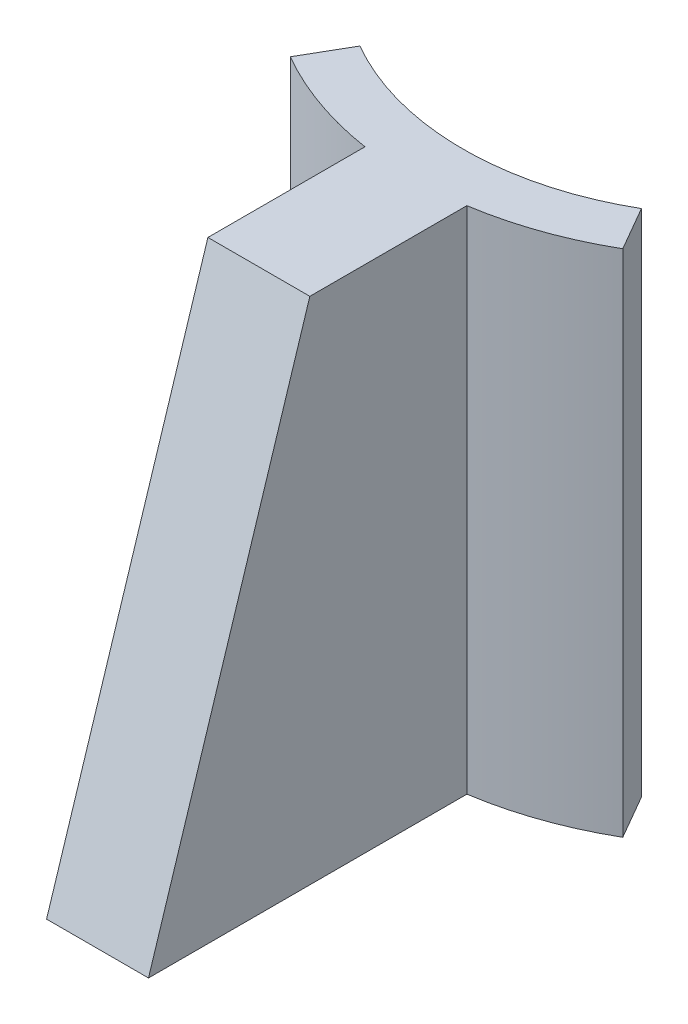
SolidWorks part; units mm, degrees
ref_plane "Front Plane" through (0, 0, 0) normal (0, 0, 1) x (1, 0, 0)
ref_plane "Top Plane" through (0, 0, 0) normal (0, 1, 0) x (1, 0, 0)
ref_plane "Right Plane" through (0, 0, 0) normal (1, 0, 0) x (0, 0, -1)
sketch "Sketch1" plane through (0, 0, 0) normal (1, 0, 0) x (0, 0, -1)
  line L0 (-3.2619, 9) -> (-4.7638, 9)
  line L1 (-3.2619, 4) -> (-6.3465, 4)
  line L2 (-6.3465, 4) -> (-4.7638, 9)
  line L9 (-3.2619, 9) -> (-2.8366, 9)
  line L11 (-3.2619, 4) -> (-2.8366, 4)
  line L12 (-2.8366, 9) -> (-2.8366, 4)
  dimension "D1" = 7.5018
extrude "Boss-Extrude1" add sketch "Sketch1" along normal blind 0.5 and the other way blind 0.5 contours L12 L9 L0 L2 L1 L11 region at (0, 6.2574, 4.2343)
ref_plane "Plane1" through (0, 6.5, 0) normal (0, 1, 0) x (1, 0, 0)
sketch "Sketch2" plane through (0, 6.5, 0) normal (0, 1, 0) x (1, 0, 0)
  line L0 (0, -2.7619) -> (0, -3.2619)
  line L1 (-1.381, -2.3919) -> (-1.631, -2.8249)
  line L2 (1.381, -2.3919) -> (1.631, -2.8249)
  arc A0 (-1.631, -2.8249) -> (0, -3.2619) centre (0, 0) ccw
  arc A1 (-1.381, -2.3919) -> (0, -2.7619) centre (0, 0) ccw
  circle A2 centre (0, 0) radius 3.8 construction
  arc A3 (0, -3.2619) -> (1.631, -2.8249) centre (0, 0) ccw
  arc A4 (0, -2.7619) -> (1.381, -2.3919) centre (0, 0) ccw
  dimension "D3" = 0.5
  dimension "D4" = 0.5381
  dimension "D1" = 60
extrude "Boss-Extrude2" add sketch "Sketch2" along normal blind 2.5 and the other way blind 2.5 contours L2 A4 A1 L1 A0 A3
scale "Scale2" scale about origin uniform scaling yes scale factor 10
